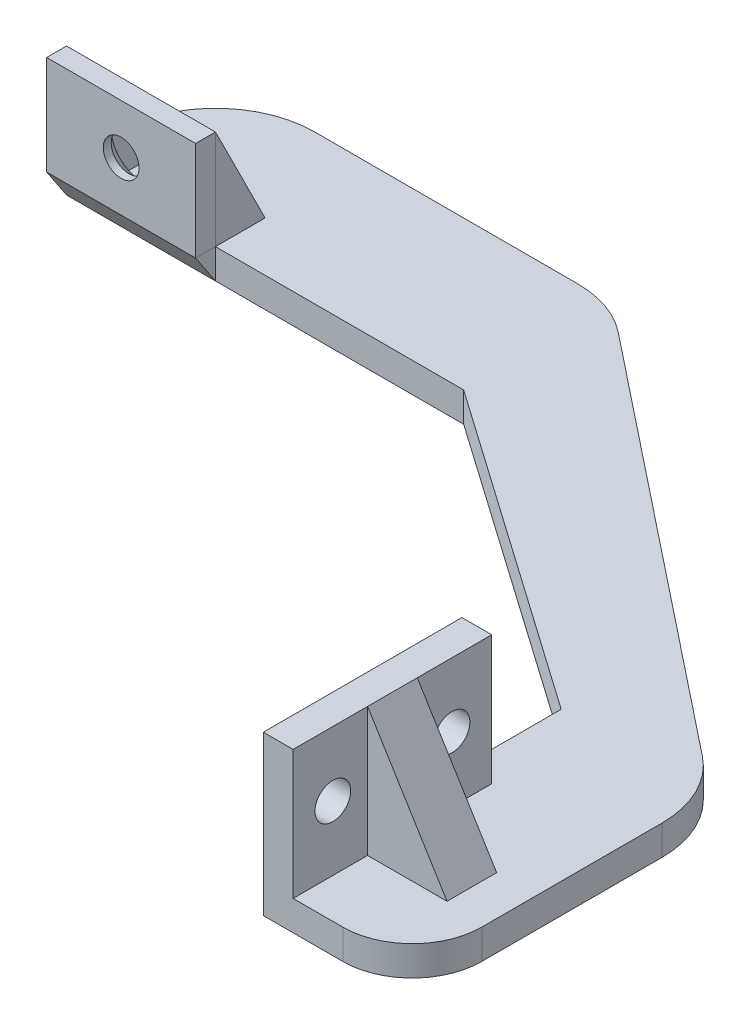
SolidWorks part; units mm, degrees
ref_plane "Front Plane" through (0, 0, 0) normal (0, 0, 1) x (1, 0, 0)
ref_plane "Top Plane" through (0, 0, 0) normal (0, 1, 0) x (1, 0, 0)
ref_plane "Right Plane" through (0, 0, 0) normal (1, 0, 0) x (0, 0, -1)
sketch "Base" plane through (0, 0, 0) normal (0, 1, 0) x (1, 0, 0)
  line L0 (20, 7.5) -> (67.7661, -30.4431)
  line L1 (20, -7.5) -> (-20, -7.5)
  line L3 (20, 7.5) -> (-20, 7.5)
  line L4 (-20, -7.5) -> (-20, 7.5)
  line L5 (20, -7.5) -> (-20, 7.5) construction
  line L6 (20, 7.5) -> (-20, -7.5) construction
  line L8 (52.7661, -30.4431) -> (20, -7.5)
  line L10 (52.7661, -30.4431) -> (52.7661, -60.4431)
  line L11 (52.7661, -60.4431) -> (67.7661, -60.4431)
  line L12 (67.7661, -30.4431) -> (67.7661, -60.4431)
  point P0 (0, 0)
  dimension "D1" = 15
  dimension "D2" = 40
  dimension "D3" = 40
  dimension "D4" = 145
  dimension "D5" = 30
extrude "Base EXT" add sketch "Base" along normal blind 3
sketch "Mounting Plate" plane through (0, 3, 0) normal (0, 1, 0) x (1, 0, 0)
  line L2 (-20, -7.5) -> (-5, -7.5)
  line L3 (-20, -7.5) -> (-20, -9.5)
  line L4 (-20, -9.5) -> (-5, -9.5)
  line L7 (-5, -7.5) -> (-5, -9.5)
  dimension "D1" = 2
  dimension "D2" = 15
extrude "LED Box Plate EXT" add sketch "Mounting Plate" along normal blind 10
sketch "Sketch16" plane through (-20, 0, 0) normal (-1, 0, 0) x (0, 0, 1)
  line L0 (2.5, 3) -> (7.5, 13)
  line L1 (-7.5, 3) -> (7.5, 3) construction
  line L2 (7.5, 13) -> (7.5, 3) construction
  line L3 (2.5, 3) -> (7.5, 3)
  line L4 (7.5, 3) -> (7.5, 13)
  dimension "D1" = 5
extrude "Boss-Extrude6" add sketch "Sketch16" against normal blind 4 separate body
sketch "Sketch17" plane through (-5, 0, 0) normal (1, 0, 0) x (0, 0, -1)
  line L0 (-7.5, 13) -> (-2.5, 3)
  line L3 (-7.5, 13) -> (-7.5, 3) construction
  line L4 (-2.5, 3) -> (-7.5, 3)
  line L5 (-7.5, 3) -> (-7.5, 13)
  line L7 (-2.5, 3) -> (-7.5, 3) construction
extrude "Boss-Extrude9" add sketch "Sketch17" against normal blind 4
sketch "Sketch18" plane through (-20, 0, 0) normal (-1, 0, 0) x (0, 0, 1)
  line L0 (7.5, 0) -> (9.5, 3)
  line L1 (9.5, 3) -> (7.5, 3)
  line L2 (7.5, 3) -> (7.5, 0)
extrude "Boss-Extrude11" add sketch "Sketch18" against normal up to surface (15 mm away) separate body up to face at (-5, 8, 8.5)
sketch "M3 Screw" plane through (0, 0, 7.5) normal (0, 0, -1) x (-1, 0, 0)
  line L2 (5, 13) -> (20, 13) construction
  line L3 (12.5, 13) -> (12.5, 3) construction
  line L4 (5, 3) -> (20, 3) construction
  circle A0 centre (12.5, 8) radius 1.8
  dimension "D1" = 3.6
extrude "M3 Screw C1 Cut" cut sketch "M3 Screw" against normal through all
sketch "M3 Screw Head" plane through (0, 0, 7.5) normal (0, 0, -1) x (-1, 0, 0)
  circle A0 centre (12.5, 8) radius 3
  dimension "D1" = 6
extrude "M3 Head C1 Cut" cut sketch "M3 Screw Head" against normal blind 10 draft 45
sketch "Sketch13" plane through (0, 3, 0) normal (0, 1, 0) x (1, 0, 0)
  line L1 (52.7661, -60.4431) -> (55.7661, -60.4431)
  line L2 (52.7661, -60.4431) -> (52.7661, -40.4431)
  line L3 (52.7661, -40.4431) -> (55.7661, -40.4431)
  line L4 (55.7661, -60.4431) -> (55.7661, -40.4431)
  dimension "D1" = 20
  dimension "D2" = 3
extrude "Mount Plate BOX EXT" add sketch "Sketch13" along normal blind 13
sketch "M3 Screws" plane through (55.7661, 0, 0) normal (1, 0, 0) x (0, 0, -1)
  line L0 (-50.4431, 16) -> (-50.4431, 3) construction
  line L1 (-60.4431, 16) -> (-40.4431, 16) construction
  line L2 (-60.4431, 3) -> (-40.4431, 3) construction
  line L3 (-40.4431, 9.5) -> (-48.1005, 9.5) construction
  line L4 (-40.4431, 16) -> (-40.4431, 3) construction
  circle A0 centre (-56.4431, 9.5) radius 1.8
  circle A1 centre (-44.4431, 9.5) radius 1.8
  dimension "D1" = 3.6
  dimension "D3" = 6
extrude "M3 Screw C2 Cut" cut sketch "M3 Screws" against normal blind 8
ref_plane "Plane2" through (55.7661, 16, 50.4431) normal (0, 0, -1) x (-1, 0, 0)
sketch "Sketch23" plane through (55.7661, 16, 50.4431) normal (0, 0, -1) x (-1, 0, 0)
  line L0 (0, -13) -> (0, 0) construction
  line L1 (0, -13) -> (-8, -13)
  line L2 (-8, -13) -> (0, 0)
  line L3 (0, 0) -> (0, -13)
  dimension "D1" = 8
extrude "Boss-Extrude16" add sketch "Sketch23" along normal blind 2.5 and the other way blind 2.5
fillet "Fillet1" radius 10 1 edges at (-20, 1.5, -7.5) type face fillet first side face at (0, 1.5, -7.5) second side face at (-20, 1.5, 0)
fillet "Fillet2" radius 7 1 edges at (67.7661, 1.5, 60.4431) type face fillet first side face at (67.7661, 1.5, 45.4431) second side face at (58.7661, 6.3333, 60.4431)
fillet "Fillet3" radius 10 1 edges at (67.7661, 1.5, 30.4431) type face fillet first side face at (67.7661, 1.5, 41.9431) second side face at (43.883, 1.5, 11.4715)
fillet "Fillet4" radius 10 1 edges at (20, 1.5, -7.5) type face fillet first side face at (41.993, 1.5, 9.9702) second side face at (5, 1.5, -7.5)
equation "\"Screw_M3\"=3.6"
equation "\"D1@M3 Screws\"=\"Screw_M3\""
equation "\"D1@M3 Screw\"=\"Screw_M3\""
